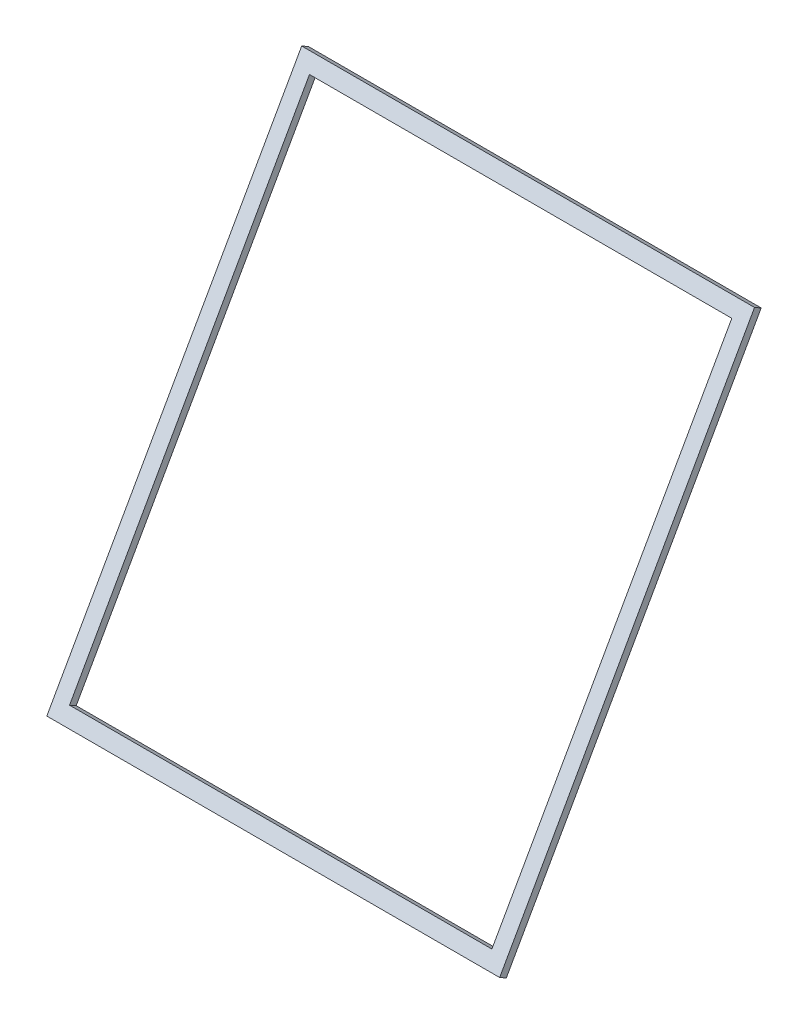
SolidWorks part; units mm, degrees
ref_plane "Alzado" through (0, 0, 0) normal (0, 0, 1) x (1, 0, 0)
ref_plane "Planta" through (0, 0, 0) normal (0, 1, 0) x (1, 0, 0)
ref_plane "Vista lateral" through (0, 0, 0) normal (1, 0, 0) x (0, 0, -1)
ref_plane "Plano1" through (0, 37.5761, 66.7597) normal (0, -0.4905, -0.8714) x (-1, 0, 0)
sketch "Croquis2" plane through (0, 37.5761, 66.7597) normal (0, -0.4905, -0.8714) x (-1, 0, 0)
  line L0 (7.7541, 166.6871) -> (7.7541, -163.3633) construction
  line L1 (-157.2459, 166.6871) -> (172.7541, 166.6871) construction
  line L2 (-130.6395, 139.4235) -> (146.1477, 139.4235)
  line L3 (-140.6395, 149.4235) -> (156.1477, 149.4235)
  line L4 (-140.6395, 149.4235) -> (-140.6395, -191.1467)
  line L5 (-140.6395, -191.1467) -> (156.1477, -191.1467)
  line L6 (156.1477, 149.4235) -> (156.1477, -191.1467)
  line L7 (-140.6395, 149.4235) -> (156.1477, -191.1467) construction
  line L8 (-140.6395, -191.1467) -> (156.1477, 149.4235) construction
  line L9 (146.1477, 139.4235) -> (146.1477, -181.1467)
  line L10 (-130.6395, -181.1467) -> (146.1477, -181.1467)
  line L11 (-130.6395, 139.4235) -> (-130.6395, -181.1467)
  point P4 (7.7541, -20.8616)
  dimension "D1" = 10
extrude "Saliente-Extruir1" add sketch "Croquis2" against normal blind 5
